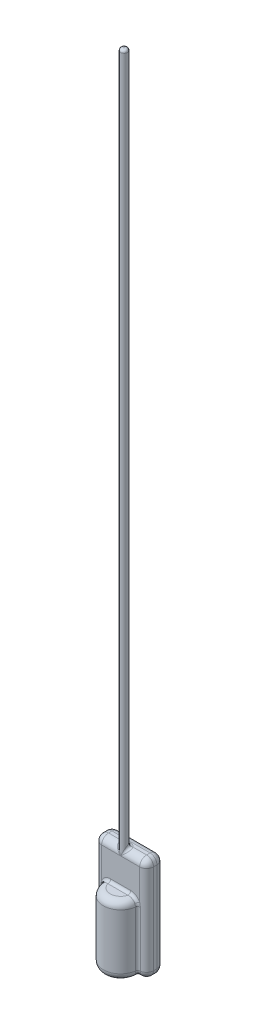
SolidWorks part; units mm, degrees
ref_plane "Front Plane" through (0, 0, 0) normal (0, 0, 1) x (1, 0, 0)
ref_plane "Top Plane" through (0, 0, 0) normal (0, 1, 0) x (1, 0, 0)
ref_plane "Right Plane" through (0, 0, 0) normal (1, 0, 0) x (0, 0, -1)
sketch "Sketch1" plane through (0, 0, 0) normal (0, 0, 1) x (1, 0, 0)
  line L1 (0, 0) -> (9.525, 0)
  line L2 (0, 0) -> (0, 19.05)
  line L3 (0, 19.05) -> (9.525, 19.05)
  line L4 (9.525, 0) -> (9.525, 19.05)
  dimension "D1" = 9.525
  dimension "D2" = 19.05
extrude "Extrude1" add sketch "Sketch1" along normal blind 3.175
sketch "Sketch2" plane through (0, 0, 0) normal (0, -1, 0) x (1, 0, 0)
  line L0 (0, 3.175) -> (9.525, 3.175) construction
  line L1 (0, 0) -> (9.525, 0) construction
  circle A0 centre (4.7625, 3.175) radius 3.175
extrude "Extrude2" add sketch "Sketch2" against normal blind 12.7
fillet "Fillet1" radius 1.27 15 edges at (9.525, 19.05, 1.5875) (0, 19.05, 1.5875) (0, 9.525, 0) (4.7625, 19.05, 0) (9.525, 9.525, 0) (9.525, 9.525, 3.175) (4.7625, 19.05, 3.175) (0, 9.525, 3.175) (4.7625, 12.7, 6.35) (4.7625, 0, 6.35) (9.525, 0, 1.5875) (0, 0, 1.5875) (4.7625, 0, 0) (0.7937, 0, 3.175) (8.7312, 0, 3.175)
sketch "Sketch3" plane through (0, 19.05, 0) normal (0, 1, 0) x (-1, 0, 0)
  line L0 (0, 1.905) -> (0, 1.27) construction
  line L1 (-1.27, 1.905) -> (-8.255, 1.905) construction
  line L2 (-8.255, 3.175) -> (-1.27, 3.175) construction
  circle A0 centre (-4.7625, 2.54) radius 0.635
  dimension "D1" = 4.7625
extrude "Extrude3" add sketch "Sketch3" along normal blind 127 and the other way blind 5.08
fillet "Fillet2" radius 0.508 7 edges at (7.7755, 0.6568, 3.0172) (7.9375, 6.35, 3.175) (1.9595, 12.328, 3.175) (7.5655, 12.328, 3.175) (1.7495, 0.6568, 3.0172) (1.5875, 6.35, 3.175) (4.7625, 12.7, 3.175)
fillet "Fillet3" radius 0.508 2 edges at (4.133, 18.9239, 2.4568) (4.133, 18.9239, 2.4568)
fillet "Fillet4" radius 0.508 1 edges at (4.7625, 146.05, 3.175)
